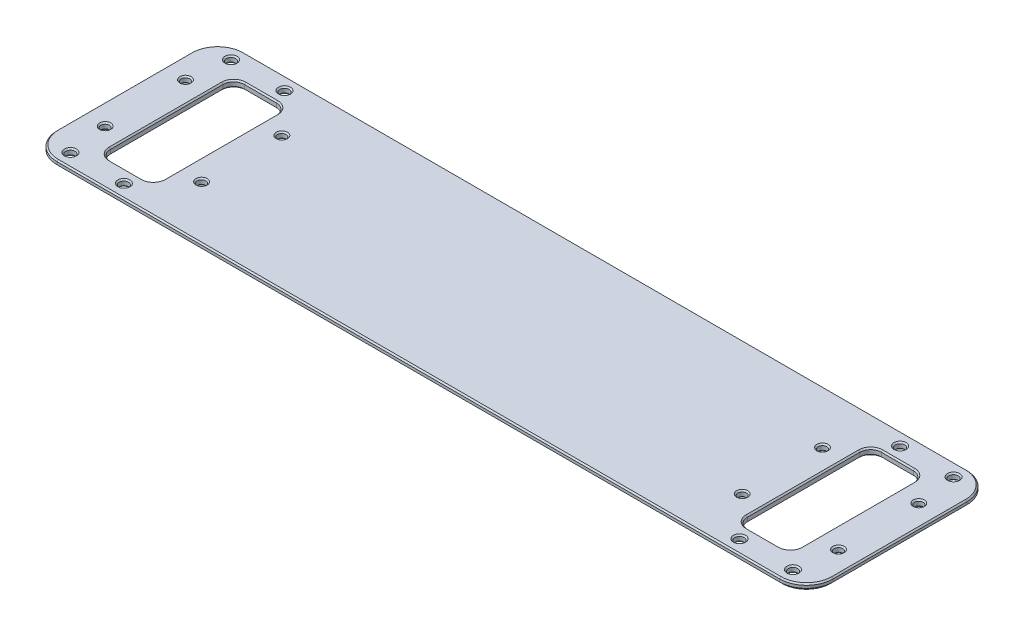
SolidWorks part; units mm, degrees
ref_plane "Front Plane" through (0, 0, 0) normal (0, 0, 1) x (1, 0, 0)
ref_plane "Top Plane" through (0, 0, 0) normal (0, 1, 0) x (1, 0, 0)
ref_plane "Right Plane" through (0, 0, 0) normal (1, 0, 0) x (0, 0, -1)
sketch "Sketch1" plane through (0, 0, 0) normal (0, 1, 0) x (1, 0, 0)
  line L0 (128.27, 0) -> (-128.27, 0) construction
  line L1 (184.15, 44.45) -> (-184.15, 44.45)
  line L2 (184.15, 44.45) -> (184.15, -44.45)
  line L3 (184.15, -44.45) -> (-184.15, -44.45)
  line L4 (-184.15, 44.45) -> (-184.15, -44.45)
  line L5 (184.15, 44.45) -> (-184.15, -44.45) construction
  line L6 (184.15, -44.45) -> (-184.15, 44.45) construction
  line L7 (-128.27, 19.05) -> (-128.27, -19.05) construction
  line L8 (-128.27, 19.05) -> (-138.43, 19.05) construction
  line L9 (-128.27, -19.05) -> (-138.43, -19.05) construction
  line L12 (-163.83, -31.75) -> (-163.83, 31.75)
  line L15 (-138.43, -31.75) -> (-163.83, -31.75)
  line L17 (-138.43, 31.75) -> (-163.83, 31.75)
  line L18 (0, 44.45) -> (0, -44.45) construction
  line L19 (-138.43, 31.75) -> (-138.43, -31.75)
  line L20 (-163.83, 19.05) -> (-173.99, 19.05) construction
  line L21 (128.27, 19.05) -> (138.43, 19.05) construction
  line L22 (163.83, 19.05) -> (173.99, 19.05) construction
  line L23 (-163.83, -19.05) -> (-173.99, -19.05) construction
  line L24 (138.43, 31.75) -> (163.83, 31.75)
  line L25 (128.27, 19.05) -> (128.27, -19.05) construction
  line L26 (128.27, -19.05) -> (138.43, -19.05) construction
  line L27 (138.43, 31.75) -> (138.43, -31.75)
  line L28 (138.43, -31.75) -> (163.83, -31.75)
  line L29 (163.83, -31.75) -> (163.83, 31.75)
  line L30 (163.83, -19.05) -> (173.99, -19.05) construction
  line L31 (151.13, 31.75) -> (151.13, 44.45) construction
  line L32 (151.13, 38.1) -> (184.15, 38.1) construction
  line L33 (151.13, -31.75) -> (151.13, -44.45) construction
  line L34 (151.13, -38.1) -> (184.15, -38.1) construction
  line L35 (-151.13, -38.1) -> (-184.15, -38.1) construction
  line L36 (-151.13, 38.1) -> (-184.15, 38.1) construction
  circle A0 centre (-128.27, 19.05) radius 2.032
  circle A1 centre (-128.27, -19.05) radius 2.032
  circle A2 centre (-173.99, 19.05) radius 2.032
  circle A3 centre (-173.99, -19.05) radius 2.032
  circle A4 centre (173.99, 19.05) radius 2.032
  circle A5 centre (128.27, 19.05) radius 2.032
  circle A6 centre (128.27, -19.05) radius 2.032
  circle A7 centre (173.99, -19.05) radius 2.032
  circle A8 centre (171.45, -38.1) radius 2.2225
  circle A9 centre (146.05, -38.1) radius 2.2225
  circle A10 centre (171.45, 38.1) radius 2.2225
  circle A11 centre (146.05, 38.1) radius 2.2225
  circle A12 centre (-146.05, -38.1) radius 2.2225
  circle A13 centre (-171.45, -38.1) radius 2.2225
  circle A14 centre (-146.05, 38.1) radius 2.2225
  circle A15 centre (-171.45, 38.1) radius 2.2225
  point P0 (0, 0)
  point P11 (-128.27, 0)
  point P13 (-138.43, 19.05)
  point P17 (-138.43, -19.05)
  point P37 (0, 0)
  point P50 (171.45, 38.1)
  point P51 (146.05, 38.1)
  point P56 (171.45, -38.1)
  point P57 (146.05, -38.1)
  dimension "D5" = 4.064
  dimension "D6" = 12.7
  dimension "D18" = 4.445
  dimension "D1" = 368.3
  dimension "D2" = 88.9
  dimension "D3" = 128.27
  dimension "D4" = 38.1
  dimension "D7" = 10.16
  dimension "D8" = 25.4
  dimension "D9" = 63.5
  dimension "D10" = 12.7
  dimension "D11" = 12.7
  dimension "D12" = 12.7
  dimension "D13" = 10.16
  dimension "D14" = 12.7
  dimension "D15" = 38.1
  dimension "D16" = 12.7
  dimension "D17" = 38.1
extrude "Boss-Extrude1" add sketch "Sketch1" along normal blind 3.175
fillet "Fillet1" radius 5.08 4 edges at (-138.43, 1.5875, 31.75) (-163.83, 1.5875, 31.75) (-163.83, 1.5875, -31.75) (-138.43, 1.5875, -31.75)
fillet "Fillet2" radius 5.08 4 edges at (163.83, 1.5875, 31.75) (138.43, 1.5875, 31.75) (138.43, 1.5875, -31.75) (163.83, 1.5875, -31.75)
fillet "Fillet3" radius 12.7 4 edges at (184.15, 1.5875, 44.45) (184.15, 1.5875, -44.45) (-184.15, 1.5875, 44.45) (-184.15, 1.5875, -44.45)
chamfer "Chamfer3" distance 0.635 angle 45 32 edges at (162.3421, 3.175, -30.2621) (151.13, 3.175, -31.75) (139.9179, 3.175, -30.2621) (163.83, 3.175, 0) (162.3421, 3.175, 30.2621) (151.13, 3.175, 31.75) (139.9179, 3.175, 30.2621) (138.43, 3.175, 0) (139.9179, 0, -30.2621) (151.13, 0, -31.75) (162.3421, 0, -30.2621) (163.83, 0, 0) (162.3421, 0, 30.2621) (151.13, 0, 31.75) (139.9179, 0, 30.2621) (138.43, 0, 0) (-139.9179, 3.175, 30.2621) (-151.13, 3.175, 31.75) (-138.43, 3.175, 0) (-139.9179, 3.175, -30.2621) (-151.13, 3.175, -31.75) (-162.3421, 3.175, 30.2621) (-162.3421, 3.175, -30.2621) (-163.83, 3.175, 0) (-139.9179, 0, 30.2621) (-151.13, 0, 31.75) (-138.43, 0, 0) (-139.9179, 0, -30.2621) (-151.13, 0, -31.75) (-162.3421, 0, 30.2621) (-163.83, 0, 0) (-162.3421, 0, -30.2621)
chamfer "Chamfer4" distance 1.27 angle 45 8 edges at (180.4303, 0, -40.7303) (0, 0, -44.45) (-180.4303, 0, -40.7303) (-184.15, 0, 0) (-180.4303, 0, 40.7303) (0, 0, 44.45) (180.4303, 0, 40.7303) (184.15, 0, 0)
chamfer "Chamfer5" distance 0.635 angle 45 16 edges at (-173.99, 0, 21.082) (-173.99, 0, -17.018) (-128.27, 0, -17.018) (-128.27, 0, 21.082) (173.99, 0, 17.018) (173.99, 0, -21.082) (128.27, 0, 17.018) (128.27, 0, -21.082) (-171.45, 0, -40.3225) (-146.05, 0, -40.3225) (-146.05, 0, 35.8775) (-171.45, 0, 35.8775) (146.05, 0, 40.3225) (171.45, 0, 40.3225) (146.05, 0, -35.8775) (171.45, 0, -35.8775)
chamfer "Chamfer6" distance 0.635 angle 45 8 edges at (180.4303, 3.175, 40.7303) (184.15, 3.175, 0) (180.4303, 3.175, -40.7303) (0, 3.175, 44.45) (-180.4303, 3.175, 40.7303) (-184.15, 3.175, 0) (0, 3.175, -44.45) (-180.4303, 3.175, -40.7303)
chamfer "Chamfer7" distance 0.635 angle 45 16 edges at (-173.99, 3.175, 21.082) (-173.99, 3.175, -17.018) (-128.27, 3.175, -17.018) (-128.27, 3.175, 21.082) (128.27, 3.175, 17.018) (128.27, 3.175, -21.082) (173.99, 3.175, -21.082) (173.99, 3.175, 17.018) (146.05, 3.175, -35.8775) (171.45, 3.175, -35.8775) (146.05, 3.175, 40.3225) (171.45, 3.175, 40.3225) (-146.05, 3.175, -40.3225) (-171.45, 3.175, -40.3225) (-171.45, 3.175, 35.8775) (-146.05, 3.175, 35.8775)
